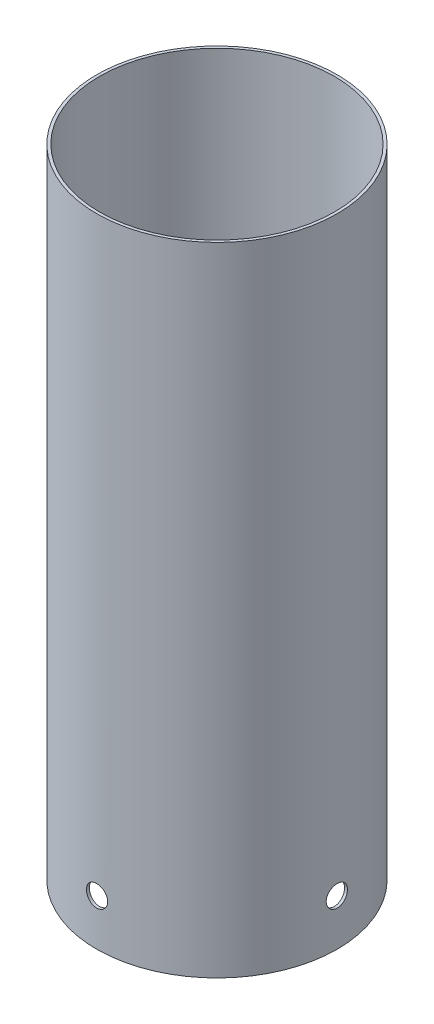
SolidWorks part; units mm, degrees
material "Helius Poly CF"
ref_plane "Front Plane" through (0, 0, 0) normal (0, 0, 1) x (1, 0, 0)
ref_plane "Top Plane" through (0, 0, 0) normal (0, 1, 0) x (1, 0, 0)
ref_plane "Right Plane" through (0, 0, 0) normal (1, 0, 0) x (0, 0, -1)
sketch "Sketch1" plane through (0, 0, 0) normal (0, 1, 0) x (1, 0, 0)
  circle A0 centre (0, 0) radius 83
  dimension "D1" = 166
extrude "Extrude-Thin1" add sketch "Sketch1" along normal blind 450 thin contours A0 thin type one direction wall 2
sketch "Sketch2" plane through (0, 0, 0) normal (0, 0, 1) x (1, 0, 0)
  line L0 (-85, 0) -> (85, 0) construction
  circle A0 centre (0, 32.7) radius 7.5
  dimension "D2" = 15
  dimension "D1" = 32.7
extrude "Cut-Extrude1" cut sketch "Sketch2" against normal blind 100 and the other way blind 100
pattern_circular "CirPattern1" count 2 every 90 about axis through (0, 450, 0) along (0, -1, 0) of "Cut-Extrude1"
